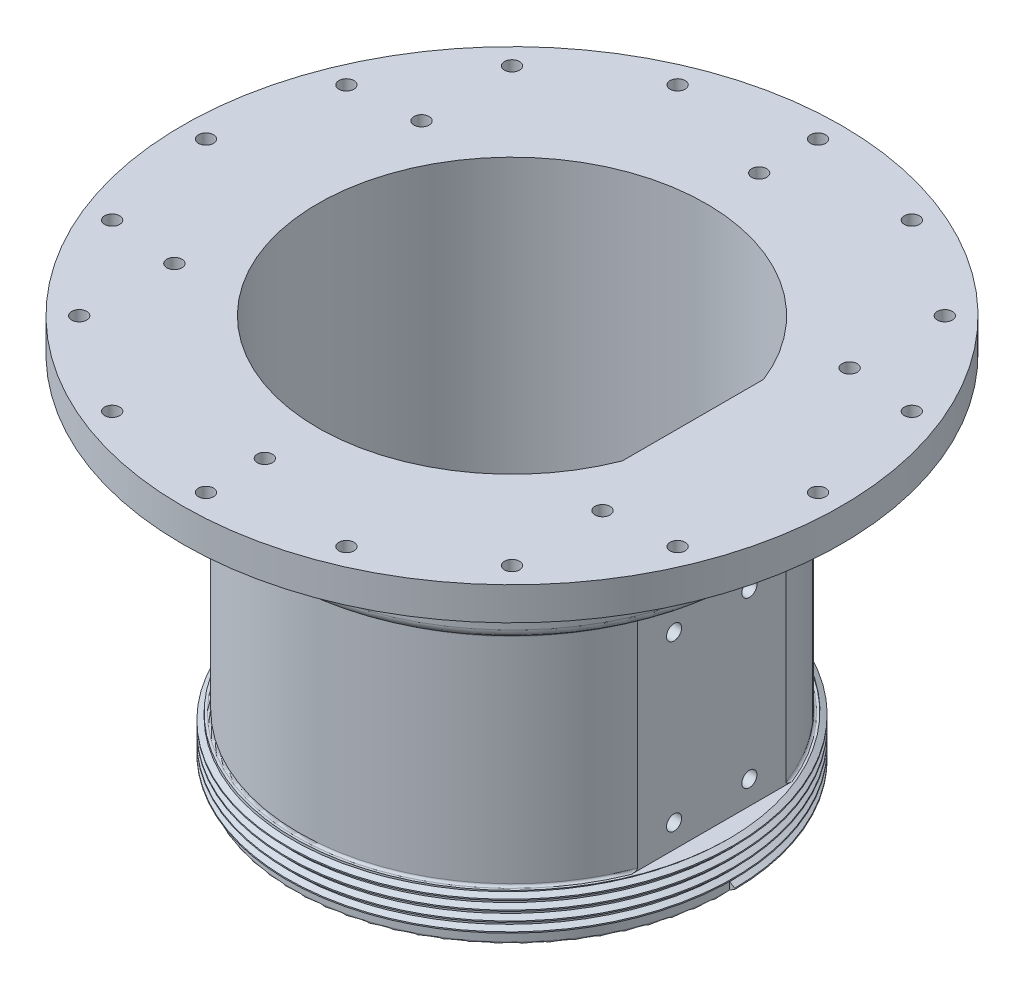
SolidWorks part; units mm, degrees
ref_plane "Front Plane" through (0, 0, 0) normal (0, 0, 1) x (1, 0, 0)
ref_plane "Top Plane" through (0, 0, 0) normal (0, 1, 0) x (1, 0, 0)
ref_plane "Right Plane" through (0, 0, 0) normal (1, 0, 0) x (0, 0, -1)
sketch "Sketch1" plane through (0, 0, 0) normal (0, 1, 0) x (1, 0, 0)
  circle A0 centre (0, 0) radius 49.25
  circle A1 centre (0, 0) radius 55 construction
  circle A2 centre (0, 0) radius 60
  circle A3 centre (0, 0) radius 52.5 construction
  circle A4 centre (0, 52.5) radius 1.6
  circle A5 centre (45.4663, 26.25) radius 1.6
  circle A6 centre (45.4663, -26.25) radius 1.6
  circle A7 centre (0, -52.5) radius 1.6
  circle A8 centre (-45.4663, -26.25) radius 1.6
  circle A9 centre (-45.4663, 26.25) radius 1.6
  point P20 (0, 0)
  dimension "D1" = 110
  dimension "D2" = 98.5
  dimension "D3" = 120
  dimension "D4" = 105
  dimension "D5" = 3.2
  dimension "D6" = 6
extrude "Boss-Extrude1" add sketch "Sketch1" along normal blind 7
sketch "Sketch2" plane through (0, 7, 0) normal (0, 1, 0) x (1, 0, 0)
  line L0 (0, 0) -> (29.4576, 0) construction
  line L1 (29.4576, 12.5) -> (60, 12.5) construction
  line L2 (29.4576, 12.5) -> (29.4576, -12.5) construction
  line L3 (29.4576, -12.5) -> (60, -12.5) construction
  line L4 (60, 12.5) -> (60, -12.5) construction
  circle A0 centre (0, 0) radius 49.25
  circle A2 centre (0, 0) radius 49.25 construction
  circle A3 centre (0, 0) radius 32 construction
  circle A5 centre (0, 0) radius 60 construction
  circle A6 centre (0, 0) radius 45.25
  dimension "D1" = 4
  dimension "D2" = 64
  dimension "D3" = 25
extrude "Boss-Extrude2" add sketch "Sketch2" against normal blind 25
sketch "Sketch6" plane through (0, 7, 0) normal (0, 1, 0) x (1, 0, 0)
  line L1 (38.4261, 15) -> (60, 15)
  line L2 (38.4261, 15) -> (38.4261, -15)
  line L3 (38.4261, -15) -> (60, -15)
  line L4 (60, 15) -> (60, -15)
  circle A0 centre (0, 0) radius 45.25
  circle A1 centre (0, 0) radius 41.25
  circle A2 centre (0, 0) radius 45.25 construction
  circle A3 centre (0, 0) radius 60 construction
  point P11 (38.4261, 0)
  circle M14 centre (0, 0) radius 45.25
  dimension "D1" = 4
  dimension "D2" = 30
extrude "Boss-Extrude5" add sketch "Sketch6" against normal blind 78 contours A1 L1 L3 M14 | L2 A1 | A1 L3 L1 M14
sketch "Sketch7" plane through (0, -71, 0) normal (0, -1, 0) x (1, 0, 0)
  line L0 (38.4261, -15) -> (38.4261, 15) construction
  line L1 (42.4261, 15.735) -> (60, 15.735)
  line L2 (42.4261, 15.735) -> (42.4261, -15.735)
  line L3 (42.4261, -15.735) -> (60, -15.735)
  line L4 (60, 15.735) -> (60, -15.735)
  circle A0 centre (0, 0) radius 45.25 construction
  circle A1 centre (0, 0) radius 45.25 construction
  circle A2 centre (0, 0) radius 60 construction
  point P9 (42.4261, 0)
  dimension "D1" = 4
extrude "Cut-Extrude3" cut sketch "Sketch7" against normal up to surface (53 mm away) up to face at (0, -18, 45.25)
sketch "Sketch8" plane through (0, -71, 0) normal (0, -1, 0) x (1, 0, 0)
  circle A0 centre (0, 0) radius 45.25
  arc A1 (42.4261, 15.735) -> (42.4261, -15.735) centre (0, 0) ccw construction
  circle A2 centre (0, 0) radius 32
  circle A3 centre (0, 0) radius 37.75 construction
  circle A4 centre (26.6933, 26.6933) radius 1.6
  circle A5 centre (37.75, 0) radius 1.6
  circle A6 centre (26.6933, -26.6933) radius 1.6
  circle A7 centre (0, -37.75) radius 1.6
  circle A8 centre (-26.6933, -26.6933) radius 1.6
  circle A9 centre (-37.75, 0) radius 1.6
  circle A10 centre (-26.6933, 26.6933) radius 1.6
  circle A11 centre (0, 37.75) radius 1.6
  point P19 (0, 0)
  dimension "D1" = 7.5
  dimension "D2" = 64
  dimension "D3" = 3.2
  dimension "D4" = 8
extrude "Boss-Extrude6" add sketch "Sketch8" along normal blind 5
sketch "Sketch9" plane through (42.4261, 0, 0) normal (1, 0, 0) x (0, 0, -1)
  line L0 (15.735, -71) -> (-15.735, -71) construction
  line L1 (-8, -26) -> (8, -26) construction
  line L2 (-8, -26) -> (-8, -61) construction
  line L3 (-8, -61) -> (8, -61) construction
  line L4 (8, -26) -> (8, -61) construction
  circle A0 centre (-8, -26) radius 1.6
  circle A1 centre (8, -26) radius 1.6
  circle A2 centre (8, -61) radius 1.6
  circle A3 centre (-8, -61) radius 1.6
  point P4 (0, -26)
  dimension "D4" = 3.2
  dimension "D1" = 16
  dimension "D2" = 35
  dimension "D3" = 10
extrude "Cut-Extrude4" cut sketch "Sketch9" against normal up to surface (4 mm away) up to face at (38.4261, -45, 0)
fillet "Fillet1" radius 2 4 edges at (0, -18, 49.25) (-45.25, -18, 0) (42.4261, -18, 0) (0, -76, -45.25)
sketch "Sketch10" plane through (0, 0, 0) normal (1, 0, 0) x (0, 0, -1)
  line L0 (-49.25, -8) -> (-45.75, -8) construction
  line L1 (-49.25, -5.6) -> (-45.75, -5.6)
  line L2 (-49.25, -5.6) -> (-49.25, -10.4)
  line L3 (-49.25, -10.4) -> (-45.75, -10.4)
  line L4 (-45.75, -5.6) -> (-45.75, -10.4)
  line L5 (-49.25, 0) -> (-49.25, -16) construction
  line L6 (0, 0) -> (0, -16) construction
  line L7 (-49.25, 0) -> (49.25, 0) construction
  line L8 (-49.25, -16) -> (49.25, -16) construction
  dimension "D1" = 3.5
  dimension "D2" = 4.8
revolve "Cut-Revolve1" cut sketch "Sketch10" angle 360 about L6
sketch "Sketch11" plane through (0, 7, 0) normal (0, 1, 0) x (1, 0, 0)
  circle A0 centre (0, 0) radius 60
  circle A1 centre (0, 0) radius 70
  circle A2 centre (0, 0) radius 60 construction
  circle A3 centre (0, 0) radius 65 construction
  circle A4 centre (0, 65) radius 1.6
  circle A5 centre (24.8744, 60.0522) radius 1.6
  circle A6 centre (45.9619, 45.9619) radius 1.6
  circle A7 centre (60.0522, 24.8744) radius 1.6
  circle A8 centre (65, 0) radius 1.6
  circle A9 centre (60.0522, -24.8744) radius 1.6
  circle A10 centre (45.9619, -45.9619) radius 1.6
  circle A11 centre (24.8744, -60.0522) radius 1.6
  circle A12 centre (0, -65) radius 1.6
  circle A13 centre (-24.8744, -60.0522) radius 1.6
  circle A14 centre (-45.9619, -45.9619) radius 1.6
  circle A15 centre (-60.0522, -24.8744) radius 1.6
  circle A16 centre (-65, 0) radius 1.6
  circle A17 centre (-60.0522, 24.8744) radius 1.6
  circle A18 centre (-45.9619, 45.9619) radius 1.6
  circle A19 centre (-24.8744, 60.0522) radius 1.6
  point P42 (0, 0)
  dimension "D1" = 10
  dimension "D2" = 5
  dimension "D3" = 3.2
  dimension "D4" = 16
extrude "Boss-Extrude7" add sketch "Sketch11" against normal up to surface (7 mm away) up to face at (0, 0, 60)
sketch "Sketch14" plane through (0, -76, 0) normal (0, -1, 0) x (1, 0, 0)
  circle A0 centre (0, 0) radius 43.25
  circle A1 centre (0, 0) radius 46.25
  circle A5 centre (0, 0) radius 43.25 construction
  dimension "D1" = 3
extrude "Boss-Extrude8" add sketch "Sketch14" against normal blind 10
sketch "Sketch15" plane through (0, -66, 0) normal (0, 1, 0) x (1, 0, 0)
  line L0 (42.4261, 15.735) -> (42.4261, -15.735)
  line L1 (42.4261, 15.735) -> (42.4261, 18.4144)
  line L2 (42.4261, -15.735) -> (42.4261, -18.4144)
  circle A0 centre (0, 0) radius 46.25
  circle A1 centre (0, 0) radius 46.25 construction
  circle M2 centre (0, 0) radius 46.25
  line M4 (42.4261, 15.735) -> (42.4261, 8.4019)
  arc M5 (42.4261, 8.4019) -> (42.4261, -8.4019) centre (0, 0) cw
  line M6 (42.4261, -8.4019) -> (42.4261, -15.735)
extrude "Boss-Extrude10" add sketch "Sketch15" against normal blind 10 contours L2 L1 M6 M2 M4 M5 | L0 M5
fillet "Fillet2" radius 0.5 2 edges at (-45.25, -66, 0) (0, -76, -46.25)
fillet "Fillet3" radius 0.5 4 edges at (0, -10.4, 49.25) (0, -10.4, 45.75) (0, -5.6, 45.75) (0, -5.6, 49.25)
thread "Thread3" pitch 2 start angle 0, offset 0, length 8.5, pitch 2, diameter 92.5
ref_plane "Plane3" through (46.25, -75.5, 0) normal (0, 0, 1) x (1, 0, 0)
sketch "Thread Profile3" plane through (46.25, -75.5, 0) normal (0, 0, 1) x (1, 0, 0)
  line L0 (0, 0) -> (0, 2) construction
  line L1 (0, 0) -> (1.0825, 0.625)
  line L2 (1.0825, 0.625) -> (1.0825, 0.875)
  line L3 (1.0825, 0.875) -> (0, 1.5)
  line L4 (1.0825, 0.75) -> (0, 0.75) construction
  line L11 (0, 0) -> (0, 1.5)
  point P2 (0, 0)
  dimension "Pitch" = 2
  dimension "Profile_Angle" = 60
  dimension "Profile_Land" = 0.25
  dimension "Profile_Height" = 1.0825
